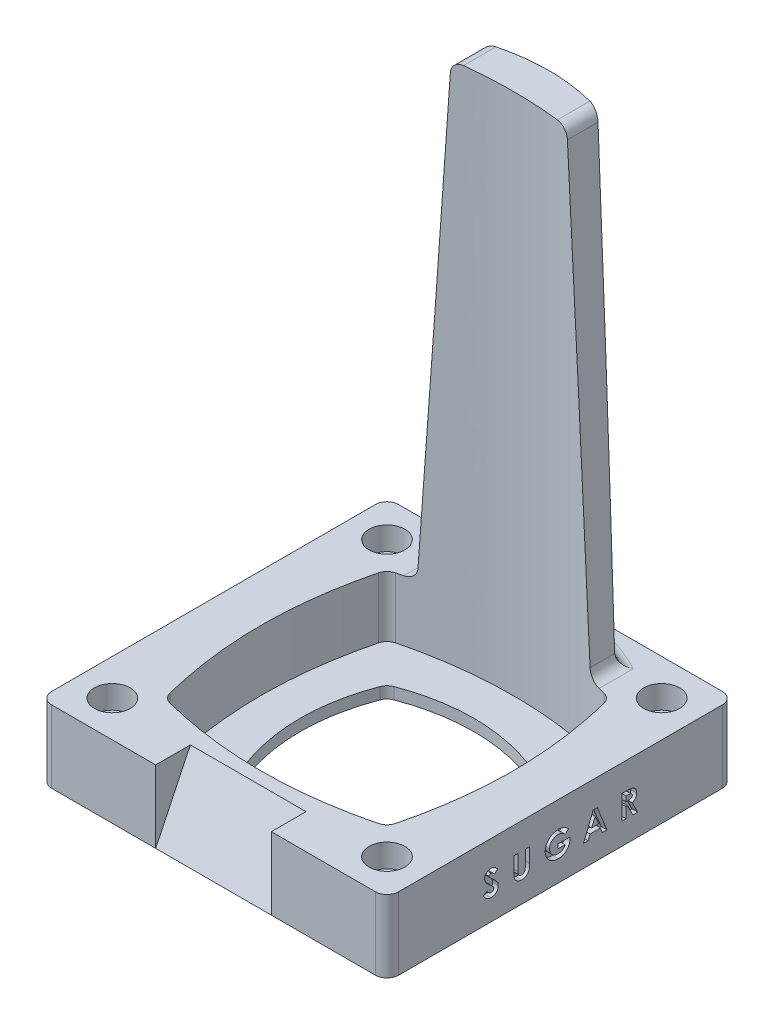
SolidWorks part; units mm, degrees
ref_plane "Front Plane" through (0, 0, 0) normal (0, 0, 1) x (1, 0, 0)
ref_plane "Top Plane" through (0, 0, 0) normal (0, 1, 0) x (1, 0, 0)
ref_plane "Right Plane" through (0, 0, 0) normal (1, 0, 0) x (0, 0, -1)
sketch "Sketch1" plane through (0, 0, 0) normal (0, 1, 0) x (1, 0, 0)
  line L1 (-38.1, -38.1) -> (38.1, -38.1)
  line L2 (-38.1, -38.1) -> (-38.1, 38.1)
  line L3 (-38.1, 38.1) -> (38.1, 38.1)
  line L4 (38.1, -38.1) -> (38.1, 38.1)
  line L5 (-38.1, -38.1) -> (38.1, 38.1) construction
  line L6 (-38.1, 38.1) -> (38.1, -38.1) construction
  point P0 (0, 0)
  dimension "D1" = 76.2
  dimension "D2" = 76.2
extrude "Boss-Extrude1" add sketch "Sketch1" along normal blind 15.875
sketch "Sketch2" plane through (0, 15.875, 0) normal (0, 1, 0) x (1, 0, 0)
  line L0 (-27.686, 0) -> (29.454, 0) construction
  line L1 (-24.384, -24.384) -> (24.384, -24.384) construction
  line L2 (-24.384, -24.384) -> (-24.384, 24.384) construction
  line L3 (-24.384, 24.384) -> (24.384, 24.384) construction
  line L4 (24.384, -24.384) -> (24.384, 24.384) construction
  line L5 (-24.384, -24.384) -> (24.384, 24.384) construction
  line L6 (-24.384, 24.384) -> (24.384, -24.384) construction
  line L7 (-27.686, -27.686) -> (27.686, -27.686) construction
  line L8 (-27.686, -27.686) -> (-27.686, 27.686) construction
  line L9 (-27.686, 27.686) -> (27.686, 27.686) construction
  line L10 (27.686, -27.686) -> (27.686, 27.686) construction
  line L11 (-27.686, -27.686) -> (27.686, 27.686) construction
  line L12 (-27.686, 27.686) -> (27.686, -27.686) construction
  line L13 (0, 27.686) -> (0, -27.686) construction
  spline S0 degree 2 poles (-24.384, 24.384) (-30.988, 0) (-24.384, -24.384) knots 0 0 0 1 1 1
  spline S1 degree 2 poles (-24.384, 24.384) (0, 30.988) (24.384, 24.384) knots 0 0 0 1 1 1
  spline S2 degree 2 poles (24.384, 24.384) (30.988, 0) (24.384, -24.384) knots 0 0 0 1 1 1
  spline S3 degree 2 poles (24.384, -24.384) (0, -30.988) (-24.384, -24.384) knots 0 0 0 1 1 1
  point P0 (0, 0)
  point P6 (0, 0)
  dimension "D1" = 48.768
  dimension "D2" = 48.768
  dimension "D3" = 55.372
  dimension "D4" = 55.372
extrude "Cut-Extrude1" cut sketch "Sketch2" against normal blind 13.335
sketch "Sketch4" plane through (0, 15.875, 0) normal (0, 1, 0) x (1, 0, 0)
  line L1 (-30.1625, -30.1625) -> (30.1625, -30.1625) construction
  line L2 (-30.1625, -30.1625) -> (-30.1625, 30.1625) construction
  line L3 (-30.1625, 30.1625) -> (30.1625, 30.1625) construction
  line L4 (30.1625, -30.1625) -> (30.1625, 30.1625) construction
  line L5 (-30.1625, -30.1625) -> (30.1625, 30.1625) construction
  line L6 (-30.1625, 30.1625) -> (30.1625, -30.1625) construction
  circle A0 centre (-30.1625, 30.1625) radius 2.54
  circle A1 centre (30.1625, 30.1625) radius 2.54
  circle A2 centre (30.1625, -30.1625) radius 2.54
  circle A3 centre (-30.1625, -30.1625) radius 2.54
  point P0 (0, 0)
  dimension "D3" = 5.08
  dimension "D4" = 5.08
  dimension "D5" = 5.08
  dimension "D6" = 5.08
  dimension "D1" = 60.325
  dimension "D2" = 60.325
extrude "Cut-Extrude3" cut sketch "Sketch4" against normal through all
fillet "Fillet2" radius 2.54 4 edges at (-38.1, 7.9375, 38.1) (38.1, 7.9375, 38.1) (38.1, 7.9375, -38.1) (-38.1, 7.9375, -38.1)
sketch "Sketch8" plane through (0, 2.54, 0) normal (0, 1, 0) x (1, 0, 0)
  line L0 (-19.05, 0) -> (29.3905, 0) construction
  line L1 (-15.875, -15.875) -> (15.875, -15.875) construction
  line L2 (-15.875, -15.875) -> (-15.875, 15.875) construction
  line L3 (-15.875, 15.875) -> (15.875, 15.875) construction
  line L4 (15.875, -15.875) -> (15.875, 15.875) construction
  line L5 (-15.875, -15.875) -> (15.875, 15.875) construction
  line L6 (-15.875, 15.875) -> (15.875, -15.875) construction
  line L7 (-19.05, -19.05) -> (19.05, -19.05) construction
  line L8 (-19.05, -19.05) -> (-19.05, 19.05) construction
  line L9 (-19.05, 19.05) -> (19.05, 19.05) construction
  line L10 (19.05, -19.05) -> (19.05, 19.05) construction
  line L11 (-19.05, -19.05) -> (19.05, 19.05) construction
  line L12 (-19.05, 19.05) -> (19.05, -19.05) construction
  line L13 (0, 19.05) -> (0, -19.05) construction
  spline S0 degree 2 poles (-15.875, 15.875) (-22.225, 0) (-15.875, -15.875) knots 0 0 0 1 1 1
  spline S1 degree 2 poles (-15.875, 15.875) (0, 22.225) (15.875, 15.875) knots 0 0 0 1 1 1
  spline S2 degree 2 poles (15.875, 15.875) (22.225, 0) (15.875, -15.875) knots 0 0 0 1 1 1
  spline S3 degree 2 poles (15.875, -15.875) (0, -22.225) (-15.875, -15.875) knots 0 0 0 1 1 1
  point P0 (0, 0)
  point P5 (0, 0)
  dimension "D1" = 38.1
  dimension "D2" = 31.75
  dimension "D3" = 31.75
  dimension "D4" = 38.1
  dimension "D5" = 0
  dimension "D6" = 0
extrude "Cut-Extrude4" cut sketch "Sketch8" against normal through all
fillet "Fillet3" radius 2.54 8 edges at (15.875, 1.27, -15.875) (15.875, 1.27, 15.875) (-15.875, 1.27, 15.875) (-15.875, 1.27, -15.875) (-24.384, 9.2075, -24.384) (-24.384, 9.2075, 24.384) (24.384, 9.2075, 24.384) (24.384, 9.2075, -24.384)
sketch "Sketch9" plane through (0, 15.875, 0) normal (0, 1, 0) x (1, 0, 0)
  line L0 (-26.67, 26.67) -> (-24.384, 24.384)
  line L1 (-27.686, -27.686) -> (27.686, -27.686) construction
  line L2 (-27.686, -27.686) -> (-27.686, 27.686) construction
  line L3 (-27.686, 27.686) -> (27.686, 27.686) construction
  line L4 (27.686, -27.686) -> (27.686, 27.686) construction
  line L5 (-27.686, -27.686) -> (27.686, 27.686) construction
  line L6 (-27.686, 27.686) -> (27.686, -27.686) construction
  line L7 (-24.384, -24.384) -> (24.384, -24.384) construction
  line L8 (-24.384, -24.384) -> (-24.384, 24.384) construction
  line L9 (-24.384, 24.384) -> (24.384, 24.384) construction
  line L10 (24.384, -24.384) -> (24.384, 24.384) construction
  line L11 (-24.384, -24.384) -> (24.384, 24.384) construction
  line L12 (-24.384, 24.384) -> (24.384, -24.384) construction
  line L13 (-30.48, -35.56) -> (30.48, -35.56) construction
  line L14 (-30.48, -35.56) -> (-30.48, 35.56) construction
  line L15 (-30.48, 35.56) -> (30.48, 35.56) construction
  line L16 (30.48, -35.56) -> (30.48, 35.56) construction
  line L17 (-30.48, -35.56) -> (30.48, 35.56) construction
  line L18 (-30.48, 35.56) -> (30.48, -35.56) construction
  line L19 (26.67, -26.67) -> (-26.67, -26.67) construction
  line L20 (26.67, -26.67) -> (26.67, 26.67) construction
  line L21 (26.67, 26.67) -> (-26.67, 26.67) construction
  line L22 (-26.67, -26.67) -> (-26.67, 26.67) construction
  line L23 (26.67, -26.67) -> (-26.67, 26.67) construction
  line L24 (26.67, 26.67) -> (-26.67, -26.67) construction
  line L25 (26.67, 26.67) -> (24.384, 24.384)
  spline S0 degree 2 poles (-24.384, 24.384) (0, 30.988) (24.384, 24.384) knots 0 0 0 1 1 1
  spline S1 degree 2 poles (-26.67, 26.67) (0, 44.45) (26.67, 26.67) knots 0 0 0 1 1 1
  point P0 (0, 0)
  point P6 (0, 0)
  point P12 (0, 0)
  point P17 (0, 0)
  dimension "D1" = 55.372
  dimension "D2" = 55.372
  dimension "D3" = 48.768
  dimension "D4" = 48.768
  dimension "D5" = 71.12
  dimension "D6" = 60.96
  dimension "D7" = 53.34
  dimension "D8" = 53.34
extrude "Boss-Extrude2" add sketch "Sketch9" along normal blind 101.6
sketch "Sketch10" plane through (0, 0, 0) normal (0, 0, 1) x (1, 0, 0)
  line L0 (0, 122.457) -> (0, 0) construction
  line L1 (-12.7, 117.475) -> (-19.05, 15.875)
  line L2 (24.384, 117.475) -> (-24.384, 117.475) construction
  line L3 (-35.56, 15.875) -> (35.56, 15.875) construction
  line L4 (12.7, 117.475) -> (19.05, 15.875)
  line L7 (-12.7, 117.475) -> (-26.67, 117.475)
  line L8 (-26.67, 117.475) -> (-26.67, 15.875)
  line L9 (-26.67, 15.875) -> (-19.05, 15.875)
  line L10 (12.7, 117.475) -> (26.67, 117.475)
  line L11 (26.67, 117.475) -> (26.67, 15.875)
  line L12 (26.67, 15.875) -> (19.05, 15.875)
  dimension "D1" = 12.7
  dimension "D2" = 19.05
extrude "Cut-Extrude5" cut sketch "Sketch10" against normal through all
fillet "Fillet4" radius 2.54 2 edges at (12.7, 117.475, -30.1672) (-12.7, 117.475, -30.1672)
sketch "Sketch11" plane through (0, 0, 0) normal (1, 0, 0) x (0, 0, -1)
  line L0 (-30.48, 15.875) -> (-38.1, 0)
  line L1 (35.56, 15.875) -> (-35.56, 15.875) construction
  line L2 (-38.1, 0) -> (-38.1, 15.875)
  line L3 (-38.1, 15.875) -> (-30.48, 15.875)
  dimension "D1" = 7.62
extrude "Cut-Extrude6" cut sketch "Sketch11" against normal mid plane 25.4
sketch "Sketch13" plane through (0, 15.875, 0) normal (0, 1, 0) x (1, 0, 0)
  circle A0 centre (30.1625, 30.1625) radius 3.937
  circle A1 centre (30.1625, -30.1625) radius 3.937
  circle A2 centre (-30.1625, -30.1625) radius 3.937
  circle A3 centre (-30.1625, 30.1625) radius 3.937
  dimension "D1" = 7.874
  dimension "D2" = 7.874
  dimension "D3" = 7.874
  dimension "D4" = 7.874
extrude "Cut-Extrude8" cut sketch "Sketch13" against normal blind 5.08
fillet "Fillet5" radius 2.54 3 edges at (19.05, 15.875, -28.3475) (-19.05, 15.875, -28.3475)
sketch "Sketch14" plane through (-38.1, 0, 0) normal (-1, 0, 0) x (0, 0, 1)
  line L0 (-35.56, 7.9375) -> (35.56, 7.9375) construction
  line L1 (-35.56, 15.875) -> (-35.56, 0) construction
  line L2 (35.56, 0) -> (35.56, 15.875) construction
  line L3 (-35.56, 4.7625) -> (35.56, 4.7625) construction
  text T0 "<b>SUGAR</b>" font "Century Gothic" height in points 20
  dimension "D1" = 3.175
extrude "Cut-Extrude9" cut sketch "Sketch14" against normal blind 1.27
sketch "Sketch15" plane through (38.1, 0, 0) normal (1, 0, 0) x (0, 0, -1)
  line L0 (-35.56, 4.7625) -> (35.56, 4.7625) construction
  line L1 (-35.56, 15.875) -> (-35.56, 0) construction
  line L2 (35.56, 0) -> (35.56, 15.875) construction
  text T0 "<b>SUGAR</b>" font "Century Gothic" height in points 20
  point P6 (-35.56, 7.9375)
  dimension "D1" = 3.175
extrude "Cut-Extrude10" cut sketch "Sketch15" against normal blind 1.27
